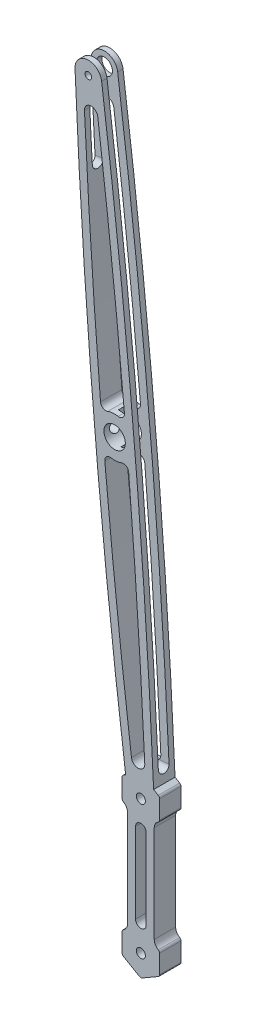
SolidWorks part; units mm, degrees
material "A2017"
ref_plane "正面" through (0, 0, 0) normal (0, 0, 1) x (1, 0, 0)
ref_plane "平面" through (0, 0, 0) normal (0, 1, 0) x (1, 0, 0)
ref_plane "右側面" through (0, 0, 0) normal (1, 0, 0) x (0, 0, -1)
sketch "ｽｹｯﾁ1" plane through (0, 0, 0) normal (0, 0, 1) x (1, 0, 0)
  line L0 (0, 0) -> (9.0749, 0) construction
  line L1 (0, 25) -> (0, 0) construction
  line L2 (0, -16.9171) -> (7, -20.9585)
  line L3 (7, 20.9585) -> (7, 29.0415)
  line L4 (7, 29.0415) -> (0, 33.0829)
  line L5 (0, 33.0829) -> (-7, 29.0415)
  line L6 (-7, 29.0415) -> (-7, 20.9585)
  line L7 (-7, 20.9585) -> (0, 16.9171)
  line L8 (0, 16.9171) -> (7, 20.9585)
  line L9 (-7, -20.9585) -> (0, -16.9171)
  line L10 (-7, -29.0415) -> (-7, -20.9585)
  line L11 (0, -33.0829) -> (-7, -29.0415)
  line L12 (7, -29.0415) -> (0, -33.0829)
  line L13 (7, -20.9585) -> (7, -29.0415)
  circle A0 centre (0, 25) radius 3
  circle A1 centre (0, -25) radius 3
  circle A2 centre (0, 25) radius 7 construction
  circle A3 centre (0, -25) radius 7 construction
  dimension "D1" = 6
  dimension "D2" = 50
  dimension "D3" = 14
extrude "ﾎﾞｽ - 押し出し1" add sketch "ｽｹｯﾁ1" along normal mid plane 8
sketch "ｽｹｯﾁ2" plane through (0, 0, 4) normal (0, 0, 1) x (1, 0, 0)
  line L0 (-7, 20.9585) -> (0, 16.9171) construction
  line L1 (5, -19.8038) -> (-5, -19.8038)
  line L2 (5, -19.8038) -> (5, 19.8038)
  line L3 (5, 19.8038) -> (-5, 19.8038)
  line L4 (-5, -19.8038) -> (-5, 19.8038)
  line L5 (5, -19.8038) -> (-5, 19.8038) construction
  line L6 (5, 19.8038) -> (-5, -19.8038) construction
  point P0 (0, 0)
  dimension "D1" = 10
extrude "ﾎﾞｽ - 押し出し2" add sketch "ｽｹｯﾁ2" against normal up to surface (8 mm away) up to face at (0, 25, -4)
fillet "ﾌｨﾚｯﾄ1" radius 3 4 edges at (5, -19.8038, 0) (-5, 19.8038, 0) (-5, -19.8038, 0) (5, 19.8038, 0)
fillet "ﾌｨﾚｯﾄ2" radius 1 10 edges at (-7, 20.9585, 0) (-7, 29.0415, 0) (0, 33.0829, 0) (7, 29.0415, 0) (7, 20.9585, 0) (7, -29.0415, 0) (0, -33.0829, 0) (-7, -29.0415, 0) (-7, -20.9585, 0) (7, -20.9585, 0)
sketch "ｽｹｯﾁ3" plane through (0, 0, -4) normal (0, 0, -1) x (-1, 0, 0)
  line L0 (0, -15) -> (0, 15) construction
  line L1 (-2, -15) -> (-2, 15)
  line L2 (2, -15) -> (2, 15)
  arc A0 (-2, -15) -> (2, -15) centre (0, -15) ccw
  arc A1 (2, 15) -> (-2, 15) centre (0, 15) ccw
  point P2 (0, 0)
  dimension "D1" = 4
  dimension "D2" = 30
extrude "ｶｯﾄ - 押し出し1" cut sketch "ｽｹｯﾁ3" against normal up to surface (8 mm away) up to face at (0, 0, 4)
sketch "ｽｹｯﾁ5" plane through (0, 0, 4) normal (0, 0, 1) x (1, 0, 0)
  circle A0 centre (0, -25) radius 3 construction
  circle A1 centre (0, 25) radius 3 construction
  circle A2 centre (0, -25) radius 3
  circle A3 centre (0, 25) radius 3
extrude "ﾎﾞｽ - 押し出し3" add sketch "ｽｹｯﾁ5" against normal blind 5
sketch "ｽｹｯﾁ8" [suppressed] plane through (0, 0, -4) normal (0, 0, -1) x (-1, 0, 0)
  circle A0 centre (0, -25) radius 3 construction
  circle A1 centre (0, 25) radius 3 construction
  circle A2 centre (0, -25) radius 3
  circle A3 centre (0, 25) radius 3
extrude "ﾎﾞｽ - 押し出し4" [suppressed] add sketch "ｽｹｯﾁ8" against normal blind 5
hole_wizard "M3 すきま穴1" positions "ｽｹｯﾁ6" profile "ｽｹｯﾁ7" hole size "M3" standard "JIS" end condition through all
sketch "ｽｹｯﾁ6" plane through (0, 0, 4) normal (0, 0, -1) x (-1, 0, 0)
  point P0 (0, 25)
  point P3 (0, -25)
sketch "ｽｹｯﾁ7" plane through (0, 25, 4) normal (1, 0, 0) x (0, -1, 0)
  line L0 (0, 0) -> (0, 8)
  line L1 (0, 8) -> (1.7, 8)
  line L2 (1.7, 8) -> (1.7, 0)
  line L5 (1.7, 0) -> (0, 0)
  line L11 (0, -6.35) -> (0, 107.95) construction
  dimension "通し穴の直径" = 3.4
  dimension "通し穴の深さ" = 8
sketch "ｽｹｯﾁ9" plane through (0, 0, 4) normal (0, 0, 1) x (1, 0, 0)
  line L0 (0, 25) -> (0, 298.9535) construction
  line L1 (0, 25) -> (-19.61, 249.1438) construction
  line L2 (0, 25) -> (-19.61, 249.1438) construction
  line L3 (-7.4715, 24.3463) -> (-27.0815, 248.4901) construction
  line L4 (7.4715, 25.6537) -> (-12.1386, 249.7975) construction
  line L15 (-7, 28.4641) -> (-7, 21.5359)
  line L16 (-5, 18.0718) -> (-5, -18.0718)
  line L17 (-7, -21.5359) -> (-7, -28.4641)
  line L18 (-6.5, -29.3301) -> (-0.5, -32.7942)
  line L19 (0.5, -32.7942) -> (6.5, -29.3301)
  line L20 (7, -28.4641) -> (7, -21.5359)
  line L21 (5, -18.0718) -> (5, 18.0718)
  line L22 (7, 21.5359) -> (7, 28.4641)
  line L23 (6.5, 29.3301) -> (0.5, 32.7942)
  line L24 (-0.5, 32.7942) -> (-6.5, 29.3301)
  line L25 (-7, 28.4641) -> (-7, 21.5359)
  line L26 (-5, 18.0718) -> (-5, -18.0718)
  line L27 (-7, -21.5359) -> (-7, -28.4641)
  line L28 (-6.5, -29.3301) -> (-0.5, -32.7942)
  line L29 (0.5, -32.7942) -> (6.5, -29.3301)
  line L30 (7, -28.4641) -> (7, -21.5359)
  line L31 (5, -18.0718) -> (5, 18.0718)
  line L32 (7, 21.5359) -> (7, 28.4641)
  line L33 (6.5, 29.3301) -> (0.5, 32.7942)
  line L34 (-0.5, 32.7942) -> (-6.5, 29.3301)
  arc A0 (-7.4715, 24.3463) -> (7.4715, 25.6537) centre (0, 25) ccw construction
  arc A1 (-12.1386, 249.7975) -> (-27.0815, 248.4901) centre (-19.61, 249.1438) ccw construction
  circle A2 centre (-19.61, 249.1438) radius 5 construction
  circle A3 centre (0, 25) radius 5
  arc A4 (-14.6533, 249.8004) -> (4.9954, 25.2141) centre (-2530.1776, -83.4321) cw
  arc A5 (-24.6055, 248.9297) -> (-4.9567, 24.3434) centre (2510.5676, 357.5759) ccw
  arc A6 (-14.6533, 249.8004) -> (-24.6055, 248.9297) centre (-19.61, 249.1438) ccw
  arc A16 (-7, 21.5359) -> (-6.5, 20.6699) centre (-6, 21.5359) ccw
  arc A17 (-5, 18.0718) -> (-6.5, 20.6699) centre (-8, 18.0718) ccw
  arc A18 (-6.5, -20.6699) -> (-5, -18.0718) centre (-8, -18.0718) ccw
  arc A19 (-6.5, -20.6699) -> (-7, -21.5359) centre (-6, -21.5359) ccw
  arc A20 (-7, -28.4641) -> (-6.5, -29.3301) centre (-6, -28.4641) ccw
  arc A21 (-0.5, -32.7942) -> (0.5, -32.7942) centre (0, -31.9282) ccw
  arc A22 (6.5, -29.3301) -> (7, -28.4641) centre (6, -28.4641) ccw
  arc A23 (7, -21.5359) -> (6.5, -20.6699) centre (6, -21.5359) ccw
  arc A24 (5, -18.0718) -> (6.5, -20.6699) centre (8, -18.0718) ccw
  arc A25 (6.5, 20.6699) -> (5, 18.0718) centre (8, 18.0718) ccw
  arc A26 (6.5, 20.6699) -> (7, 21.5359) centre (6, 21.5359) ccw
  arc A27 (7, 28.4641) -> (6.5, 29.3301) centre (6, 28.4641) ccw
  arc A28 (0.5, 32.7942) -> (-0.5, 32.7942) centre (0, 31.9282) ccw
  arc A29 (-6.5, 29.3301) -> (-7, 28.4641) centre (-6, 28.4641) ccw
  arc A30 (-7, 21.5359) -> (-6.5, 20.6699) centre (-6, 21.5359) ccw
  arc A31 (-5, 18.0718) -> (-6.5, 20.6699) centre (-8, 18.0718) ccw
  arc A32 (-6.5, -20.6699) -> (-5, -18.0718) centre (-8, -18.0718) ccw
  arc A33 (-6.5, -20.6699) -> (-7, -21.5359) centre (-6, -21.5359) ccw
  arc A34 (-7, -28.4641) -> (-6.5, -29.3301) centre (-6, -28.4641) ccw
  arc A35 (-0.5, -32.7942) -> (0.5, -32.7942) centre (0, -31.9282) ccw
  arc A36 (6.5, -29.3301) -> (7, -28.4641) centre (6, -28.4641) ccw
  arc A37 (7, -21.5359) -> (6.5, -20.6699) centre (6, -21.5359) ccw
  arc A38 (5, -18.0718) -> (6.5, -20.6699) centre (8, -18.0718) ccw
  arc A39 (6.5, 20.6699) -> (5, 18.0718) centre (8, 18.0718) ccw
  arc A40 (6.5, 20.6699) -> (7, 21.5359) centre (6, 21.5359) ccw
  arc A41 (7, 28.4641) -> (6.5, 29.3301) centre (6, 28.4641) ccw
  arc A42 (0.5, 32.7942) -> (-0.5, 32.7942) centre (0, 31.9282) ccw
  arc A43 (-6.5, 29.3301) -> (-7, 28.4641) centre (-6, 28.4641) ccw
  point P4 (-9.805, 137.0719)
  dimension "D5" = 10
  dimension "D1" = 5
  dimension "D2" = 225
  dimension "D4" = 15
  dimension "D3" = 0
extrude "ﾎﾞｽ - 押し出し5" add sketch "ｽｹｯﾁ9" against normal up to surface (8 mm away) contours A4 A6 A5 L33 region at (-10.1534, 141.0541, 4) up to face at (0, 0, -4)
sketch "ｽｹｯﾁ12" plane through (0, 0, -4) normal (0, 0, -1) x (-1, 0, 0)
  line L0 (19.61, 249.1438) -> (0, 25) construction
hole_wizard "M3 ねじ穴1" positions "ｽｹｯﾁ19" profile "ｽｹｯﾁ20" tap size "M3" standard "JIS" end condition through all
sketch "ｽｹｯﾁ19" plane through (0, 0, 4) normal (0, 0, 1) x (1, 0, 0)
  point P0 (-19.61, 249.1438)
sketch "ｽｹｯﾁ20" plane through (-19.61, 249.1438, 4) normal (1, 0, 0) x (0, -1, 0)
  line L0 (0, 0) -> (0, 8)
  line L1 (0, 8) -> (1.25, 8)
  line L2 (1.25, 8) -> (1.25, 0)
  line L5 (1.25, 0) -> (0, 0)
  line L11 (0, -6.35) -> (0, 107.95) construction
  dimension "次ｻｰﾌｪｽまでのねじ下穴ﾄﾞﾘﾙ直径" = 2.5
  dimension "次ｻｰﾌｪｽまでのねじ下穴ﾄﾞﾘﾙの深さ" = 8
cosmetic thread "穴のねじ山1" parameters "D2"=3
sketch "ｽｹｯﾁ10" plane through (0, 0, 4) normal (0, 0, 1) x (1, 0, 0)
  circle A0 centre (-19.61, 249.1438) radius 3
  dimension "D1" = 6
extrude "ｶｯﾄ - 押し出し2" [suppressed] cut sketch "ｽｹｯﾁ10" against normal blind 6
sketch "ｽｹｯﾁ21" plane through (0, 0, -4) normal (0, 0, -1) x (-1, 0, 0)
  circle A0 centre (19.61, 249.1438) radius 3
  dimension "D1" = 6
extrude "ｶｯﾄ - 押し出し8" cut sketch "ｽｹｯﾁ21" against normal blind 6
ref_plane "平面1" through (2.1706, 0.1899, 0) normal (0.9962, 0.0872, 0) x (0.0872, -0.9962, 0)
sketch "ｽｹｯﾁ13" plane through (0, 0, -4) normal (0, 0, -1) x (-1, 0, 0)
  line L0 (19.61, 249.1438) -> (0, 25) construction
  arc A2 (17.6274, 249.4065) -> (-1.7741, 30.1938) centre (2530.1776, -83.4321) ccw
  arc A3 (17.6274, 249.4065) -> (-1.7741, 30.1938) centre (2530.1776, -83.4321) ccw
  arc A4 (21.0716, 237.1884) -> (16.0946, 237.6238) centre (18.5745, 237.3071) ccw
  arc A5 (2.6995, 30.1943) -> (21.6082, 249.0582) centre (-2510.5676, 357.5759) ccw
  arc A6 (2.6995, 30.1943) -> (21.6082, 249.0582) centre (-2510.5676, 357.5759) ccw
  arc A7 (-1.4616, 36.9554) -> (3.5154, 36.52) centre (1.0356, 36.8367) ccw
  dimension "D3" = 5
  dimension "D1" = 3
  dimension "D2" = 3
extrude "ｶｯﾄ - 押し出し3" cut sketch "ｽｹｯﾁ13" against normal through all contours A3 A7 A6 A4 region at (-9.805, 137.0719, -4)
sketch "ｽｹｯﾁ14" plane through (0, 0, -4) normal (0, 0, -1) x (-1, 0, 0)
  line L0 (14.2879, 136.6797) -> (5.3221, 137.4641) construction
  arc A0 (3.5154, 36.52) -> (21.0716, 237.1884) centre (-2510.5676, 357.5759) ccw construction
  arc A1 (16.0946, 237.6238) -> (-1.4616, 36.9554) centre (2530.1776, -83.4321) ccw construction
  circle A2 centre (9.805, 137.0719) radius 7.5
  arc A3 (5.6744, 29.8068) -> (24.6055, 248.9297) centre (-2510.5676, 357.5759) ccw construction
extrude "ﾎﾞｽ - 押し出し6" add sketch "ｽｹｯﾁ14" against normal up to surface (8 mm away) up to face at (-9.805, 137.0719, 4)
fillet "ﾌｨﾚｯﾄ3" radius 2 4 edges at (-4.8058, 131.481, 0) (-13.7574, 130.6978, 0) (-14.8042, 142.6628, 0) (-5.8526, 143.446, 0)
sketch "ｽｹｯﾁ15" plane through (0, 0, 4) normal (0, 0, 1) x (1, 0, 0)
  line L0 (-19.61, 249.1438) -> (0, 25) construction
  circle A0 centre (-9.805, 137.0719) radius 4
  dimension "D1" = 8
extrude "ｶｯﾄ - 押し出し4" cut sketch "ｽｹｯﾁ15" against normal through all
sketch "ｽｹｯﾁ16" plane through (2.1706, 0.1899, 0) normal (0.9962, 0.0872, 0) x (0.0872, -0.9962, 0)
  line L0 (-254.9049, 0) -> (-34.9049, 0) construction
  line L1 (-254.9049, 4) -> (-254.9049, -4) construction
  line L2 (-254.9049, 2) -> (-34.9049, 2)
  line L3 (-254.9049, -2) -> (-34.9049, -2)
  arc A0 (-254.9049, 2) -> (-254.9049, -2) centre (-254.9049, 0) ccw
  arc A1 (-34.9049, -2) -> (-34.9049, 2) centre (-34.9049, 0) ccw
  point P5 (-144.9049, 0)
  dimension "D1" = 4
  dimension "D2" = 220
extrude "ｶｯﾄ - 押し出し6" cut sketch "ｽｹｯﾁ16" along normal through all
sketch "ｽｹｯﾁ22" plane through (2.1706, 0.1899, 0) normal (0.9962, 0.0872, 0) x (0, 0, -1)
  line L0 (0, 254.9049) -> (0, 219.9049) construction
  line L1 (-2, 254.9049) -> (2, 254.9049) construction
  line L2 (2, 254.9049) -> (2, 219.9049)
  line L3 (-2, 254.9049) -> (-2, 219.9049)
  line L4 (2, 252.9049) -> (2, 254.9049) construction
  arc A0 (2, 254.9049) -> (-2, 254.9049) centre (0, 254.9049) ccw
  arc A1 (-2, 219.9049) -> (2, 219.9049) centre (0, 219.9049) ccw
  point P5 (0, 237.4049)
  dimension "D1" = 35
extrude "ｶｯﾄ - 押し出し9" cut sketch "ｽｹｯﾁ22" against normal through all
sketch "ｽｹｯﾁ23" plane through (2.1706, 0.1899, 0) normal (0.9962, 0.0872, 0) x (0, 0, -1)
  line L0 (0, 129.9049) -> (0, 144.9049) construction
  line L1 (2, 129.9049) -> (-2, 129.9049) construction
  line L2 (-2, 144.9049) -> (2, 144.9049) construction
  circle A0 centre (0, 137.4049) radius 2
  dimension "D1" = 4
extrude "ｶｯﾄ - 押し出し10" cut sketch "ｽｹｯﾁ23" against normal through all
